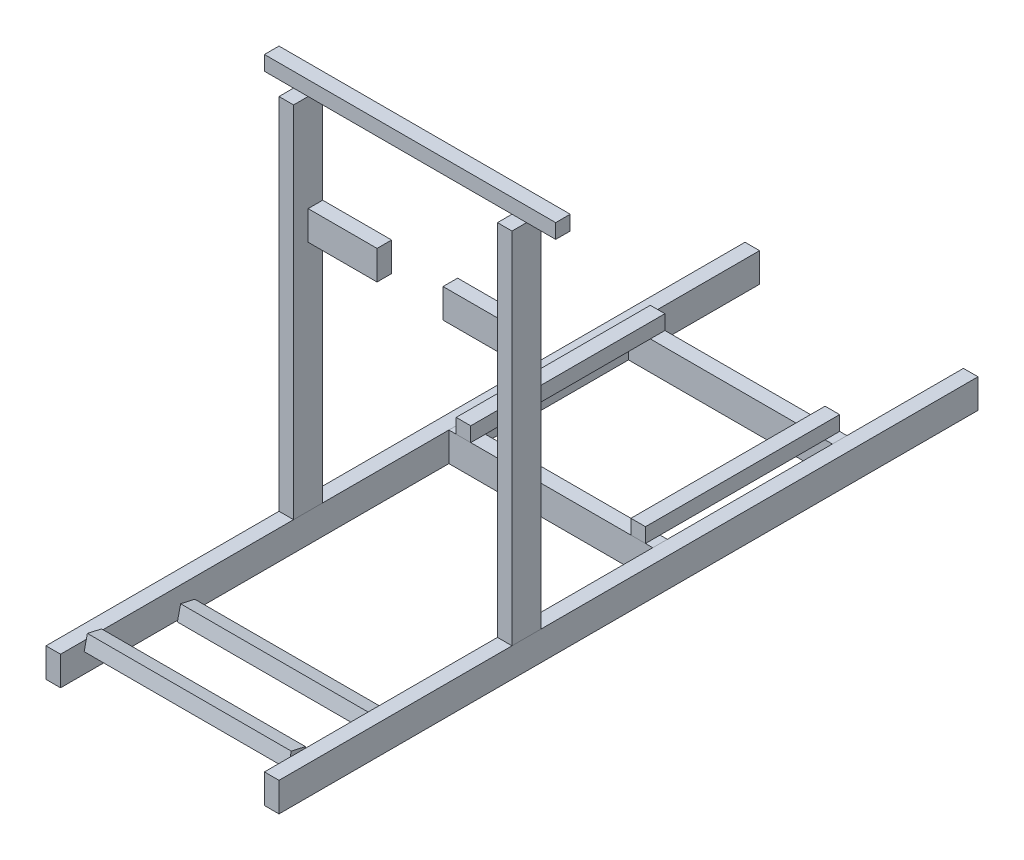
SolidWorks part; units mm, degrees
material "6061-T6 (SS)"
ref_plane "Front Plane" through (0, 0, 0) normal (0, 0, 1) x (1, 0, 0)
ref_plane "Top Plane" through (0, 0, 0) normal (0, 1, 0) x (1, 0, 0)
ref_plane "Right Plane" through (0, 0, 0) normal (1, 0, 0) x (0, 0, -1)
sketch "Sketch1" plane through (0, 0, 0) normal (0, 0, 1) x (1, 0, 0)
  line L0 (0, -90.2611) -> (0, 372.4246) construction
  line L1 (-266.7, 19.05) -> (-266.7, 95.25)
  line L2 (266.7, 19.05) -> (304.8, 19.05)
  line L3 (266.7, 19.05) -> (266.7, 95.25)
  line L4 (266.7, 95.25) -> (304.8, 95.25)
  line L5 (304.8, 19.05) -> (304.8, 95.25)
  line L6 (-266.7, 19.05) -> (-304.8, 19.05)
  line L7 (-304.8, 19.05) -> (-304.8, 95.25)
  line L8 (-266.7, 95.25) -> (-304.8, 95.25)
  dimension "D2" = 76.2
  dimension "D1" = 533.4
  dimension "D4" = 19.05
extrude "Boss-Extrude1" add sketch "Sketch1" against normal blind 1828.8
sketch "Sketch2" plane through (0, 0, 0) normal (1, 0, 0) x (0, 0, -1)
  line L0 (1828.8, 19.05) -> (0, 19.05) construction
  line L1 (1524, 95.25) -> (1485.9, 95.25)
  line L2 (1524, 95.25) -> (1524, 19.05)
  line L3 (1524, 19.05) -> (1485.9, 19.05)
  line L4 (1485.9, 95.25) -> (1485.9, 19.05)
  line L5 (1054.1, 95.25) -> (1016, 95.25)
  line L6 (1054.1, 95.25) -> (1054.1, 19.05)
  line L7 (1054.1, 19.05) -> (1016, 19.05)
  line L8 (1016, 95.25) -> (1016, 19.05)
  line L10 (0, 19.05) -> (0, 95.25) construction
  dimension "D1" = 38.1
  dimension "D2" = 76.2
  dimension "D4" = 38.1
  dimension "D3" = 76.2
  dimension "D5" = 508
  dimension "D6" = 1016
extrude "Boss-Extrude2" add sketch "Sketch2" along normal up to next (266.7 mm away) and the other way up to next (266.7 mm away) separate body
sketch "Sketch3" plane through (0, 95.25, 0) normal (0, 1, 0) x (1, 0, 0)
  line L0 (0, -1000) -> (0, 49000) construction
  line L1 (-266.7, 609.6) -> (-266.7, 685.8)
  line L2 (266.7, 609.6) -> (304.8, 609.6)
  line L3 (266.7, 609.6) -> (266.7, 685.8)
  line L4 (266.7, 685.8) -> (304.8, 685.8)
  line L5 (304.8, 609.6) -> (304.8, 685.8)
  line L6 (-266.7, 609.6) -> (-304.8, 609.6)
  line L7 (-304.8, 609.6) -> (-304.8, 685.8)
  line L8 (-266.7, 685.8) -> (-304.8, 685.8)
  line L9 (266.7, 1828.8) -> (266.7, 0) construction
  line L10 (304.8, 0) -> (266.7, 0) construction
  dimension "D1" = 38.1
  dimension "D2" = 76.2
  dimension "D3" = 609.6
extrude "Boss-Extrude3" add sketch "Sketch3" along normal blind 939.8 separate body
sketch "Sketch4" plane through (0, 0, -1016) normal (0, 0, 1) x (1, 0, 0)
  line L0 (0, -1002.4675) -> (0, 48997.5325) construction
  line L1 (-209.55, 133.35) -> (-209.55, 95.25)
  line L2 (209.55, 133.35) -> (247.65, 133.35)
  line L3 (209.55, 133.35) -> (209.55, 95.25)
  line L4 (209.55, 95.25) -> (247.65, 95.25)
  line L5 (247.65, 133.35) -> (247.65, 95.25)
  line L6 (-209.55, 133.35) -> (-247.65, 133.35)
  line L7 (-247.65, 133.35) -> (-247.65, 95.25)
  line L8 (-209.55, 95.25) -> (-247.65, 95.25)
  line L9 (-266.7, 95.25) -> (266.7, 95.25) construction
  point P13 (228.6, 133.35)
  point P14 (-228.6, 133.35)
  dimension "D1" = 38.1
  dimension "D2" = 38.1
  dimension "D3" = 457.2
extrude "Boss-Extrude4" add sketch "Sketch4" against normal blind 508 separate body
sketch "Sketch6" plane through (0, 0, 0) normal (1, 0, 0) x (0, 0, -1)
  line L0 (61.7895, 70.1417) -> (70.1417, 107.3149)
  line L25 (70.1417, 107.3149) -> (107.3149, 98.9627)
  line L26 (107.3149, 98.9627) -> (98.9627, 61.7895)
  line L27 (0, 76.2) -> (49.0625, 76.2) construction
  line L28 (98.9627, 61.7895) -> (61.7895, 70.1417)
  line L29 (0, 38.1) -> (55.8026, 38.1) construction
  line L30 (1828.8, 95.25) -> (0, 95.25) construction
  line L31 (1828.8, 19.05) -> (0, 19.05) construction
  line L32 (305.7085, 15.3373) -> (314.0607, 52.5105)
  line L33 (314.0607, 52.5105) -> (351.2339, 44.1583)
  line L34 (351.2339, 44.1583) -> (342.8817, 6.9851)
  line L35 (342.8817, 6.9851) -> (305.7085, 15.3373)
  line L36 (70.1417, 107.3149) -> (98.9627, 61.7895) construction
  line L37 (314.0607, 52.5105) -> (342.8817, 6.9851) construction
  line L38 (76.2, 47.3789) -> (92.9044, 121.7254) construction
  line L39 (47.3789, 92.9044) -> (121.7254, 76.2) construction
  line L40 (320.119, -7.4254) -> (336.8234, 66.9211) construction
  line L41 (291.2979, 38.1) -> (365.6444, 21.3956) construction
  line L42 (0, 19.05) -> (0, 95.25) construction
  point P13 (88.7283, 103.1388)
  point P14 (332.6473, 48.3344)
  point P21 (84.5522, 84.5522)
  point P22 (84.5522, 84.5522)
  point P23 (84.5522, 84.5522)
  point P24 (328.4712, 29.7478)
  point P25 (328.4712, 29.7478)
  point P26 (328.4712, 29.7478)
  dimension "D1" = 38.1
  dimension "D4" = 38.1
  dimension "D2" = 38.1
  dimension "D8" = 19.05
  dimension "D6" = 19.05
  dimension "D5" = 250
  dimension "D7" = 76.2
  dimension "D9" = 76.2
  dimension "D10" = 12.663
  dimension "D11" = 76.2
extrude "Boss-Extrude5" add sketch "Sketch6" along normal up to surface (266.7 mm away) and the other way up to surface (266.7 mm away) separate body up to face at (266.7, 57.15, -914.4) other way up to face at (-266.7, 57.15, -914.4)
sketch "Sketch7" plane through (0, 0, 0) normal (1, 0, 0) x (0, 0, -1)
  line L0 (685.8, 1035.05) -> (685.8, 95.25) construction
  line L1 (685.8, 781.05) -> (647.7, 781.05)
  line L2 (685.8, 781.05) -> (685.8, 704.85)
  line L3 (685.8, 704.85) -> (647.7, 704.85)
  line L4 (647.7, 781.05) -> (647.7, 704.85)
  line L5 (1828.8, 95.25) -> (0, 95.25) construction
  dimension "D1" = 38.1
  dimension "D2" = 76.2
  dimension "D3" = 609.6
extrude "Boss-Extrude6" add sketch "Sketch7" along normal up to next (266.7 mm away) and the other way up to next (266.7 mm away) separate body
extrude "Cut-Extrude1" cut sketch "Sketch7<2>" against normal mid plane 172.7
sketch "Sketch7<2>" plane through (0, 0, 0) normal (1, 0, 0) x (0, 0, -1) same geometry as "Sketch7"
sketch "Sketch8" plane through (0, 0, 0) normal (1, 0, 0) x (0, 0, -1)
  line L1 (647.7, 1073.15) -> (685.8, 1073.15)
  line L2 (647.7, 1073.15) -> (647.7, 1035.05)
  line L3 (647.7, 1035.05) -> (685.8, 1035.05)
  line L4 (685.8, 1073.15) -> (685.8, 1035.05)
  point P4 (787.4, 1009.65)
  dimension "D1" = 38.1
  dimension "D2" = 38.1
extrude "Boss-Extrude7" add sketch "Sketch8" along normal mid plane 762 separate body
equation "\"W 1.5\"= 1.5"
equation "\"D1@Sketch2\"=\"W 1.5\""
equation "\"H 3\"= 3"
equation "\"D2@Sketch2\"=\"H 3\""
equation "\"D4@Sketch2\"=\"W 1.5\""
equation "\"D3@Sketch2\"=\"H 3\""
equation "\"D3@Sketch1\"=\"W 1.5\""
equation "\"D2@Sketch1\"=\"H 3\""
equation "\"D1@Sketch3\"=\"W 1.5\""
equation "\"D2@Sketch3\"=\"H 3\""
equation "\"H 1.5\"= 1.5"
equation "\"D1@Sketch4\"=\"W 1.5\""
equation "\"D2@Sketch4\"=\"H 1.5\""
equation "\"D1@Sketch6\"=\"W 1.5\""
equation "\"D2@Sketch6\"=\"W 1.5\""
equation "\"D3@Sketch6\"=\"H 1.5\""
equation "\"D4@Sketch6\"=\"H 1.5\""
equation "\"D1@Sketch7\"=\"W 1.5\""
equation "\"D2@Sketch7\"=\"H 3\""
equation "\"D1@Sketch8\"=\"W 1.5\""
equation "\"D2@Sketch8\"=\"H 1.5\""
